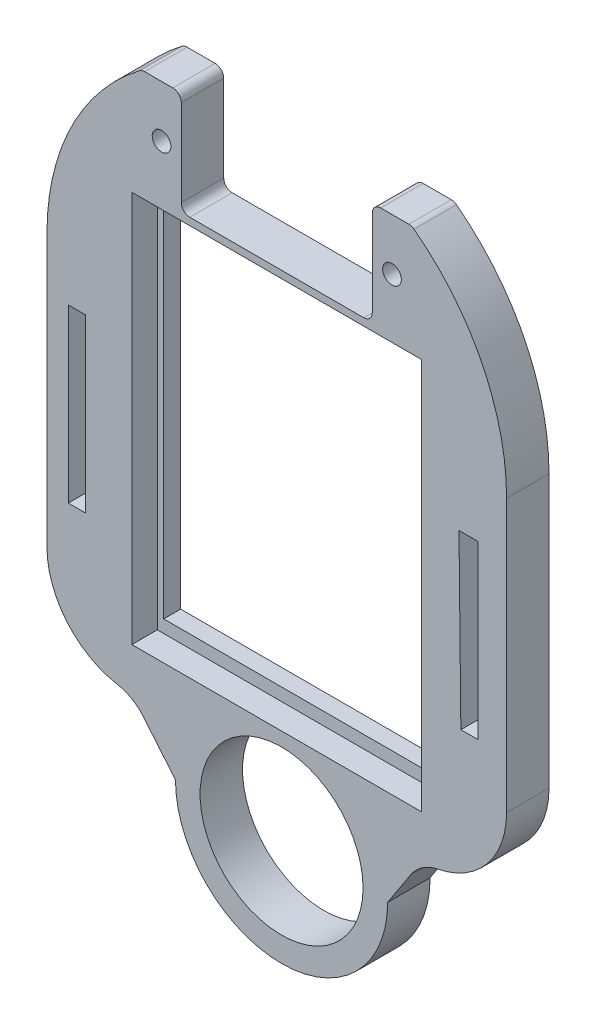
SolidWorks part; units mm, degrees
ref_plane "Plan de face" through (0, 0, 0) normal (0, 0, 1) x (1, 0, 0)
ref_plane "Plan de dessus" through (0, 0, 0) normal (0, 1, 0) x (1, 0, 0)
ref_plane "Plan de droite" through (0, 0, 0) normal (1, 0, 0) x (0, 0, -1)
sketch "Esquisse1" plane through (0, 0, 0) normal (0, 0, 1) x (1, 0, 0)
  line L8 (-20.2431, 24.4782) -> (-20.2431, -25.5218)
  line L9 (-10.2431, 22.5532) -> (23.9069, 22.5532) construction
  line L10 (-10.2431, 22.5532) -> (-10.2431, -23.5968) construction
  line L11 (-10.2431, -23.5968) -> (23.9069, -23.5968) construction
  line L12 (23.9069, 22.5532) -> (23.9069, -23.5968) construction
  line L15 (6.8319, 24.7461) -> (6.8319, -25.5968) construction
  line L20 (33.9069, 24.4782) -> (33.9069, -25.5218)
  line L27 (22.2069, 21.2482) -> (22.2069, -22.1018)
  line L28 (22.2069, 21.2482) -> (-9.4931, 21.2482)
  line L29 (-9.4931, 21.2482) -> (-9.4931, -22.1018)
  line L30 (22.2069, -22.1018) -> (-9.4931, -22.1018)
  line L35 (-20.2431, -25.5218) -> (-20.2431, -25.5968)
  line L38 (33.9069, -25.5968) -> (33.9069, -25.5218)
  line L40 (5.8319, 26.4782) -> (33.9069, 26.4782)
  line L41 (33.9069, 26.4782) -> (33.9069, 24.4782)
  line L42 (5.8319, 26.4782) -> (-20.2431, 26.4782)
  line L43 (-20.2431, 26.4782) -> (-20.2431, 24.4782)
  line L44 (6.8319, -25.5968) -> (33.9069, -25.5968)
  line L45 (6.8319, -25.5968) -> (-20.2431, -25.5968)
  point P0 (5.8319, 26.4782)
  point P5 (-20.2431, -0.5218)
  point P6 (-10.2431, -0.5218)
  point P18 (6.8319, -25.5968)
  dimension "D1" = 50
  dimension "D2" = 0
  dimension "D3" = 34.15
  dimension "D4" = 46.15
  dimension "D5" = 10
  dimension "D6" = 10
  dimension "D7" = 2
  dimension "D8" = 2
extrude "Boss.-Extru.1" add sketch "Esquisse1" along normal blind 2
sketch "Esquisse2" plane through (0, 0, 2) normal (0, 0, 1) x (1, 0, 0)
  line L8 (-11.1931, -23.4068) -> (-11.1931, 22.7432)
  line L9 (-11.1931, -23.4068) -> (22.9569, -23.4068)
  line L10 (22.9569, -23.4068) -> (22.9569, 22.7432)
  line L11 (-11.1931, 22.7432) -> (22.9569, 22.7432)
  line L22 (-20.2431, 26.4782) -> (-20.2431, -25.5968)
  line L23 (-20.2431, -25.5968) -> (33.9069, -25.5968)
  line L24 (33.9069, -25.5968) -> (33.9069, 26.4782)
  line L25 (33.9069, 26.4782) -> (-20.2431, 26.4782)
  point P12 (22.2069, -22.1018)
extrude "Boss.-Extru.2" add sketch "Esquisse2" along normal blind 3
sketch "Esquisse3" plane through (0, 0, 5) normal (0, 0, 1) x (1, 0, 0)
  line L5 (-17.7305, -9.8391) -> (-17.7305, 10.3809)
  line L6 (-17.7305, -9.8391) -> (-15.7305, -9.8391)
  line L7 (-15.7305, -9.8391) -> (-15.5105, 10.3797)
  line L8 (-17.7305, 10.3809) -> (-15.5105, 10.3797)
  line L9 (6.3945, -41.8391) -> (6.3945, 42.1609) construction
  line L10 (28.5195, -9.8391) -> (28.2995, 10.3797)
  line L11 (30.5195, 10.3809) -> (28.2995, 10.3797)
  line L12 (30.5195, -9.8391) -> (30.5195, 10.3809)
  line L13 (30.5195, -9.8391) -> (28.5195, -9.8391)
  dimension "D1" = 20.22
  dimension "D2" = 2.22
extrude "Enlèv. mat.-Extru.1" cut sketch "Esquisse3" against normal through all
fillet "Congé1" radius 10 4 edges at (33.9069, 26.4782, 2.5) (33.9069, -25.5968, 2.5) (-20.2431, -25.5968, 2.5) (-20.2431, 26.4782, 2.5)
sketch "Esquisse4" plane through (0, 0, 0) normal (0, 0, 1) x (1, 0, 0)
  line L12 (-9.0681, 38.6782) -> (-4.4181, 38.6782)
  line L13 (-4.4181, 38.6782) -> (-4.4181, 26.4782)
  line L16 (-6.7431, 38.6782) -> (-6.7431, 26.4782) construction
  line L17 (-9.0681, 32.5782) -> (-4.4181, 32.5782) construction
  line L18 (23.9069, 26.4782) -> (-10.2431, 26.4782) construction
  line L19 (-20.2431, 16.4782) -> (-20.2431, -15.5968)
  line L20 (6.8319, 26.4782) -> (6.8319, 41.5577) construction
  line L22 (22.7319, 32.5782) -> (18.0819, 32.5782) construction
  line L23 (20.4069, 38.6782) -> (20.4069, 26.4782) construction
  line L25 (22.7319, 38.6782) -> (18.0819, 38.6782)
  line L26 (18.0819, 38.6782) -> (18.0819, 26.4782)
  line L29 (-4.4181, 26.4782) -> (18.0819, 26.4782)
  line L31 (-5.1045, -31.7597) -> (-10.2431, -25.5968)
  line L32 (19.8955, -31.7597) -> (23.9069, -25.5968)
  line L33 (33.9069, 16.4782) -> (33.9069, -15.5968)
  line L35 (-17.7305, 10.3809) -> (-15.7305, 10.3809)
  line L36 (-17.7305, 10.3809) -> (-17.7305, -9.8391)
  line L37 (-17.7305, -9.8391) -> (-15.7305, -9.8391)
  line L38 (-15.7305, 10.3809) -> (-15.7305, -9.8391)
  line L39 (28.2995, 10.3797) -> (30.5195, 10.3797)
  line L40 (28.2995, 10.3797) -> (28.2995, -9.8391)
  line L41 (28.2995, -9.8391) -> (30.5195, -9.8391)
  line L42 (30.5195, 10.3797) -> (30.5195, -9.8391)
  circle A2 centre (-6.7431, 32.5782) radius 1.1
  circle A3 centre (20.4069, 32.5782) radius 1.1
  arc A5 (-5.1045, -31.7597) -> (19.8955, -31.7597) centre (7.3955, -31.7597) ccw
  arc A6 (-20.2431, -15.5968) -> (-10.2431, -25.5968) centre (-10.2431, -15.5968) ccw
  arc A9 (33.9069, -15.5968) -> (23.9069, -25.5968) centre (23.9069, -15.5968) cw
  arc A10 (-20.2431, 16.4782) -> (-9.0681, 38.6782) centre (7.3955, 16.4782) cw
  arc A11 (33.9069, 16.4782) -> (22.7319, 38.6782) centre (6.2684, 16.4782) ccw
  point P8 (7.3955, -31.7597)
  dimension "D3" = 2.2
  dimension "D6" = 25
  dimension "D1" = 4.65
  dimension "D4" = 11.25
extrude "Boss.-Extru.3" add sketch "Esquisse4" along normal blind 5
fillet "Congé2" radius 1 6 edges at (-4.4181, 26.4782, 2.5) (18.0819, 38.6782, 2.5) (-4.4181, 38.6782, 2.5) (18.0819, 26.4782, 2.5) (22.7319, 38.6782, 2.5) (-9.0681, 38.6782, 2.5)
fillet "Congé3" radius 5 2 edges at (-10.2431, -25.5968, 2.5) (23.9069, -25.5968, 2.5)
sketch "Esquisse5" plane through (0, 0, 5) normal (0, 0, 1) x (1, 0, 0)
  circle A0 centre (7.3955, -31.7597) radius 9.6
  dimension "D1" = 19.2
extrude "Enlèv. mat.-Extru.2" cut sketch "Esquisse5" against normal through all
sketch "Esquisse7" plane through (0, 0, 5) normal (0, 0, 1) x (1, 0, 0)
  line L0 (-10.2431, 25.617) -> (23.9069, 25.617)
  line L1 (-10.2431, 25.617) -> (-10.2431, -20.533)
  line L2 (-10.2431, -20.533) -> (23.9069, -20.533)
  line L3 (23.9069, 25.617) -> (23.9069, -20.533)
  line L4 (22.2069, 24.312) -> (22.2069, -19.038)
  line L5 (22.2069, 24.312) -> (-9.4931, 24.312)
  line L6 (-9.4931, 24.312) -> (-9.4931, -19.038)
  line L7 (22.2069, -19.038) -> (-9.4931, -19.038)
  line L8 (-20.2431, 0.4407) -> (33.9069, 0.4407) construction
  line L9 (-20.2431, 16.4782) -> (-20.2431, -15.5968) construction
  line L10 (33.9069, -15.5968) -> (33.9069, 16.4782) construction
  line L11 (6.8319, 0.4407) -> (6.8319, 37.8323) construction
  point P0 (-10.2431, 2.542)
extrude "Enlèv. mat.-Extru.3" cut sketch "Esquisse7" against normal through all contours L5 L6 L7 L4
extrude "Enlèv. mat.-Extru.4" cut sketch "Esquisse7<4>" against normal blind 3 contours L0 L3 L2 L1
sketch "Esquisse7<4>" plane through (0, 0, 5) normal (0, 0, 1) x (1, 0, 0) same geometry as "Esquisse7"
